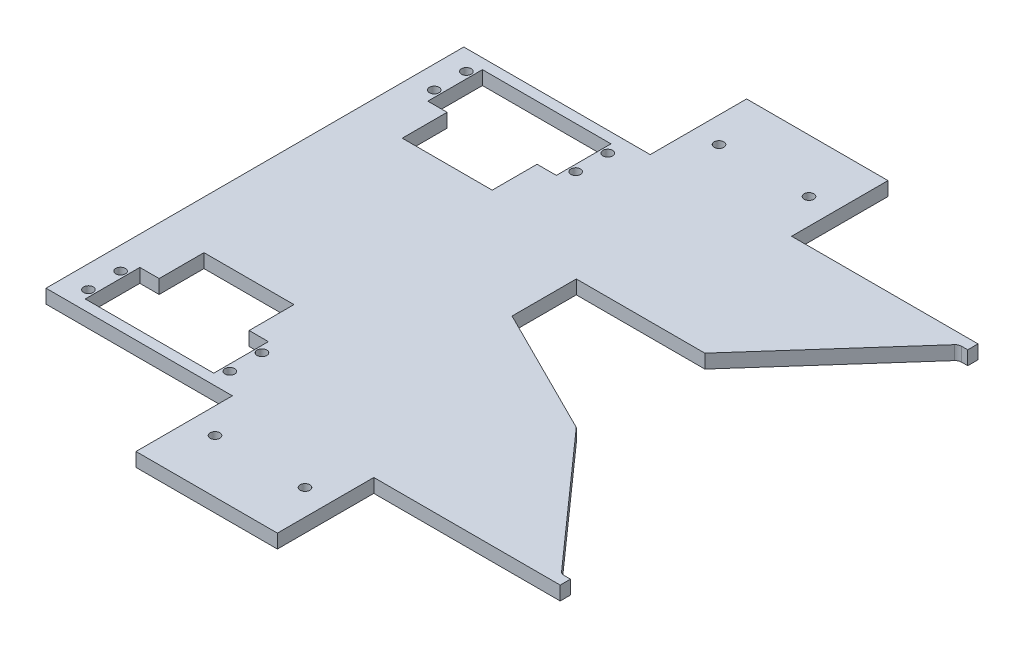
SolidWorks part; units mm, degrees
ref_plane "Front Plane" through (0, 0, 0) normal (0, 0, 1) x (1, 0, 0)
ref_plane "Top Plane" through (0, 0, 0) normal (0, 1, 0) x (1, 0, 0)
ref_plane "Right Plane" through (0, 0, 0) normal (1, 0, 0) x (0, 0, -1)
sketch "Sketch2" plane through (0, 0, 0) normal (0, 1, 0) x (1, 0, 0)
  line L2 (0, 0) -> (0, 65)
  line L3 (0, 65) -> (58, 65)
  line L4 (160, 0) -> (160, 65)
  line L8 (0, 0) -> (160, 0)
  line L9 (102, 65) -> (160, 65)
  line L11 (102, 65) -> (102, 95)
  line L12 (58, 65) -> (58, 95)
  line L13 (58, 95) -> (102, 95)
  dimension "D1" = 65
  dimension "D2" = 160
  dimension "D3" = 44
  dimension "D4" = 30
extrude "Boss-Extrude1" add sketch "Sketch2" along normal blind 4.3
mirror "Mirror1" about plane through (0, 4.3, 0) normal (0, 0, -1) of bodies 101
sketch "Sketch3" plane through (0, 4.3, 0) normal (0, 1, 0) x (1, 0, 0)
  line L0 (160, 61.8) -> (160, -61.8)
  line L1 (120.0126, 20) -> (157.1565, 61.8)
  line L3 (80.0126, 0) -> (80.0126, 20)
  line L4 (80.0126, 20) -> (120.0126, 20)
  line L12 (160, 65) -> (102, 65)
  line L13 (102, 65) -> (102, 95)
  line L15 (102, 95) -> (58, 95)
  line L16 (58, 65) -> (0, 65)
  line L17 (0, 65) -> (0, -65)
  line L18 (0, -65) -> (58, -65)
  line L20 (58, 95) -> (58, 65)
  line L22 (102, -65) -> (160, -65)
  line L23 (160, -65) -> (160, 65)
  line L36 (58, -65) -> (58, -95)
  line L38 (58, -95) -> (102, -95)
  line L39 (58, -95) -> (102, -95)
  line L40 (102, -95) -> (102, -65)
  line L42 (160, -61.8) -> (157.1556, -61.8)
  line L45 (160, 61.8) -> (157.1565, 61.8)
  line L48 (80.0126, 0) -> (120, -20)
  line L49 (120, -20) -> (157.1556, -61.8)
  line M24 (160, -65) -> (160, 65)
  dimension "D2" = 130
  dimension "D3" = 20
  dimension "D4" = 40
  dimension "D1" = 0
extrude "Cut-Extrude1" cut sketch "Sketch3" against normal blind 4.5 contours L48 L49 L1 L4 L3 M24 region at (132.7054, 4.3, -1.1594)
fillet "Fillet1" radius 2 2 edges at (157.1565, 2.15, -61.8) (157.1556, 2.15, 61.8)
ref_axis "Axis1" through (80, 4.3, 95) along (0, 0, -1)
sketch "Sketch4" plane through (0, 4.3, 0) normal (0, 1, 0) x (1, 0, 0)
  line L0 (80, -95) -> (80, 95)
  line L1 (102, -95) -> (58, -95) construction
  line L2 (102, 95) -> (58, 95) construction
ref_plane "Plane2" through (0, 4.3, 0) normal (0, 1, 0) x (1, 0, 0)
sketch "Sketch6" plane through (0, 4.3, 0) normal (0, 1, 0) x (1, 0, 0)
  line L3 (9, -61.8) -> (49, -61.8)
  line L6 (29, -45.8) -> (29, -44.8)
  line L7 (9, -44.8) -> (15, -44.8)
  line L11 (43, -44.8) -> (43, -30.8418)
  line L12 (15, -44.8) -> (15, -30.8418)
  line L13 (15, -30.8418) -> (43, -30.8418)
  line L15 (0, 0) -> (80.0126, 0)
  line L16 (80.0126, 0) -> (120, -20) construction
  line L18 (9, 44.8) -> (15, 44.8)
  line L20 (15, 30.8418) -> (43, 30.8418)
  line L21 (15, 44.8) -> (15, 30.8418)
  line L22 (43, 44.8) -> (43, 30.8418)
  line L25 (15, -45.8) -> (15, -30.8418) construction
  line L27 (9, 61.8) -> (49, 61.8)
  line L30 (4, -61.8) -> (3, -61.8)
  line L31 (0, -61.8) -> (160, -61.8) construction
  line L32 (3, -61.8) -> (4, -61.8)
  line L33 (3, -44.8) -> (3, -62.8) construction
  line L34 (3, -62.8) -> (55, -62.8) construction
  line L35 (55, -44.8) -> (55, -62.8) construction
  line L36 (4, -61.8) -> (54, -61.8) construction
  line L37 (0, 61.8) -> (160, 61.8) construction
  line L38 (54, 61.8) -> (55, 61.8)
  line L39 (54, 61.8) -> (55, 61.8)
  line L40 (43, 44.8) -> (49, 44.8)
  line L41 (4, -45.8) -> (4, -61.8) construction
  line L42 (4, -45.8) -> (54, -45.8) construction
  line L43 (43, -44.8) -> (49, -44.8)
  line L44 (3, -44.8) -> (55, -44.8) construction
  line L45 (29, -45.8) -> (29, -30.8418) construction
  line L46 (43, -45.8) -> (43, -30.8418) construction
  line L47 (54, -45.8) -> (54, -61.8) construction
  line L48 (9, -61.8) -> (49, -61.8)
  line L52 (9, 61.8) -> (9, 44.8)
  line L53 (55, 61.8) -> (54, 61.8)
  line L56 (49, 61.8) -> (49, 44.8)
  line L59 (3, -61.8) -> (4, -61.8)
  line L60 (9, -44.8) -> (9, -61.8)
  line L64 (49, -44.8) -> (49, -61.8)
  dimension "D4" = 1
  dimension "D5" = 14
  dimension "D6" = 14
extrude "Cut-Extrude2" cut sketch "Sketch6" against normal blind 10
sketch "Sketch7" plane through (0, 4.3, 0) normal (0, 1, 0) x (1, 0, 0)
  line L0 (0, 0) -> (80.0126, 0)
  line L1 (0, 65) -> (0, -65) construction
sketch "Sketch8" plane through (0, 4.3, 0) normal (0, 1, 0) x (1, 0, 0)
  circle A0 centre (7, 58.8) radius 1.5
  circle A1 centre (7, 48.8) radius 1.5
  circle A2 centre (51, 48.8) radius 1.5
  circle A3 centre (51, 58.8) radius 1.5
  circle A4 centre (7, -48.8) radius 1.5
  circle A5 centre (7, -58.8) radius 1.5
  circle A6 centre (51, -58.8) radius 1.5
  circle A7 centre (51, -48.8) radius 1.5
  dimension "D7" = 3
extrude "Cut-Extrude3" cut sketch "Sketch8" against normal blind 10
sketch "Sketch9" plane through (0, 0, 0) normal (0, -1, 0) x (1, 0, 0)
  circle A0 centre (66, 78.4) radius 1.5
  circle A1 centre (94, 78.4) radius 1.5
  circle A2 centre (66, -78.4) radius 1.5
  circle A3 centre (94, -78.4) radius 1.5
  dimension "D1" = 3
extrude "Cut-Extrude4" cut sketch "Sketch9" against normal blind 10
